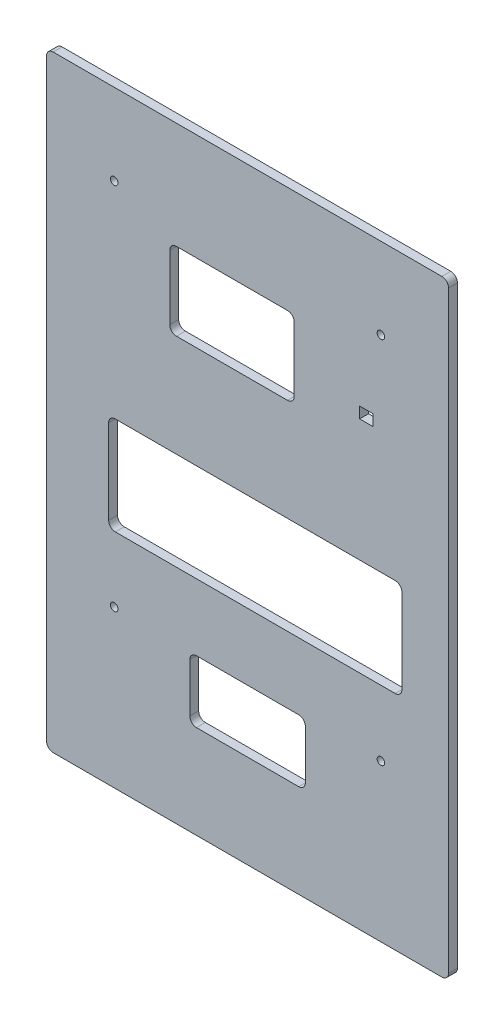
SolidWorks part; units mm, degrees
material "Verre"
ref_plane "Plan de face" through (0, 0, 0) normal (0, 0, 1) x (1, 0, 0)
ref_plane "Plan de dessus" through (0, 0, 0) normal (0, 1, 0) x (1, 0, 0)
ref_plane "Plan de droite" through (0, 0, 0) normal (1, 0, 0) x (0, 0, -1)
sketch "Esquisse1" plane through (0, 0, 0) normal (0, 0, 1) x (1, 0, 0)
  line L1 (0, 0) -> (180.86, 0)
  line L2 (0, 0) -> (0, 273)
  line L3 (0, 273) -> (180.86, 273)
  line L4 (180.86, 0) -> (180.86, 273)
  line L5 (64.43, 70) -> (116.43, 70)
  line L6 (64.43, 70) -> (64.43, 42)
  line L7 (64.43, 42) -> (116.43, 42)
  line L8 (116.43, 70) -> (116.43, 42)
  line L9 (27.93, 144) -> (159.86, 144)
  line L10 (27.93, 144) -> (27.93, 100)
  line L11 (27.93, 100) -> (159.86, 100)
  line L12 (159.86, 144) -> (159.86, 100)
  line L13 (55.43, 225) -> (111.43, 225)
  line L14 (55.43, 225) -> (55.43, 190)
  line L15 (55.43, 190) -> (111.43, 190)
  line L16 (111.43, 225) -> (111.43, 190)
  line L17 (140.86, 204) -> (146.86, 204)
  line L18 (140.86, 204) -> (140.86, 199)
  line L19 (140.86, 199) -> (146.86, 199)
  line L20 (146.86, 204) -> (146.86, 199)
  circle A0 centre (30.43, 236.5) radius 1.5
  circle A1 centre (150.43, 236.5) radius 1.5
  circle A2 centre (30.43, 70.5) radius 1.5
  circle A3 centre (150.43, 70.5) radius 1.5
  dimension "D5" = 3
  dimension "D8" = 3
  dimension "D13" = 3
  dimension "D14" = 3
  dimension "D1" = 180.86
  dimension "D2" = 273
  dimension "D3" = 30.43
  dimension "D4" = 36.5
  dimension "D6" = 36.5
  dimension "D7" = 30.43
  dimension "D9" = 30.43
  dimension "D10" = 30.43
  dimension "D11" = 70.5
  dimension "D12" = 70.5
  dimension "D15" = 64.43
  dimension "D16" = 42
  dimension "D17" = 28
  dimension "D18" = 30
  dimension "D19" = 44
  dimension "D20" = 52
  dimension "D21" = 27.93
  dimension "D22" = 21
  dimension "D23" = 48
  dimension "D24" = 35
  dimension "D25" = 55.43
  dimension "D26" = 56
  dimension "D27" = 6
  dimension "D28" = 5
  dimension "D29" = 40
  dimension "D30" = 74
extrude "Boss.-Extru.1" add sketch "Esquisse1" along normal blind 4
hole_wizard "Dégagement M31" positions "Esquisse2" profile "Esquisse3" hole size "M3" standard "ISO" end condition through all
sketch "Esquisse2" plane through (0, 0, 4) normal (0, 0, 1) x (1, 0, 0)
  point P0 (30.43, 236.5)
  point P3 (150.43, 236.5)
  point P6 (150.43, 70.5)
  point P9 (30.43, 70.5)
sketch "Esquisse3" plane through (30.43, 236.5, 4) normal (1, 0, 0) x (0, -1, 0)
  line L0 (0, 0) -> (0, 4)
  line L1 (0, 4) -> (1.7, 4)
  line L2 (1.7, 4) -> (1.7, 0)
  line L5 (1.7, 0) -> (0, 0)
  line L11 (0, -6.35) -> (0, 107.95) construction
  dimension "Diamètre du perçage jusqu'au prochain" = 3.4
  dimension "Profondeur du perçage jusqu'au prochain" = 4
fillet "Congé1" radius 3 16 edges at (0, 0, 2) (180.86, 0, 2) (116.43, 42, 2) (64.43, 42, 2) (116.43, 70, 2) (64.43, 70, 2) (159.86, 100, 2) (27.93, 100, 2) (159.86, 144, 2) (27.93, 144, 2) (180.86, 273, 2) (0, 273, 2) (111.43, 190, 2) (111.43, 225, 2) (55.43, 225, 2) (55.43, 190, 2)
equation "\"D7@Esquisse1\"=\"D3@Esquisse1\""
equation "\"D9@Esquisse1\"=\"D3@Esquisse1\""
equation "\"D10@Esquisse1\"=\"D3@Esquisse1\""
equation "\"D12@Esquisse1\"=\"D11@Esquisse1\""
equation "\"D13@Esquisse1\"=\"D5@Esquisse1\""
equation "\"D14@Esquisse1\"=\"D8@Esquisse1\""
